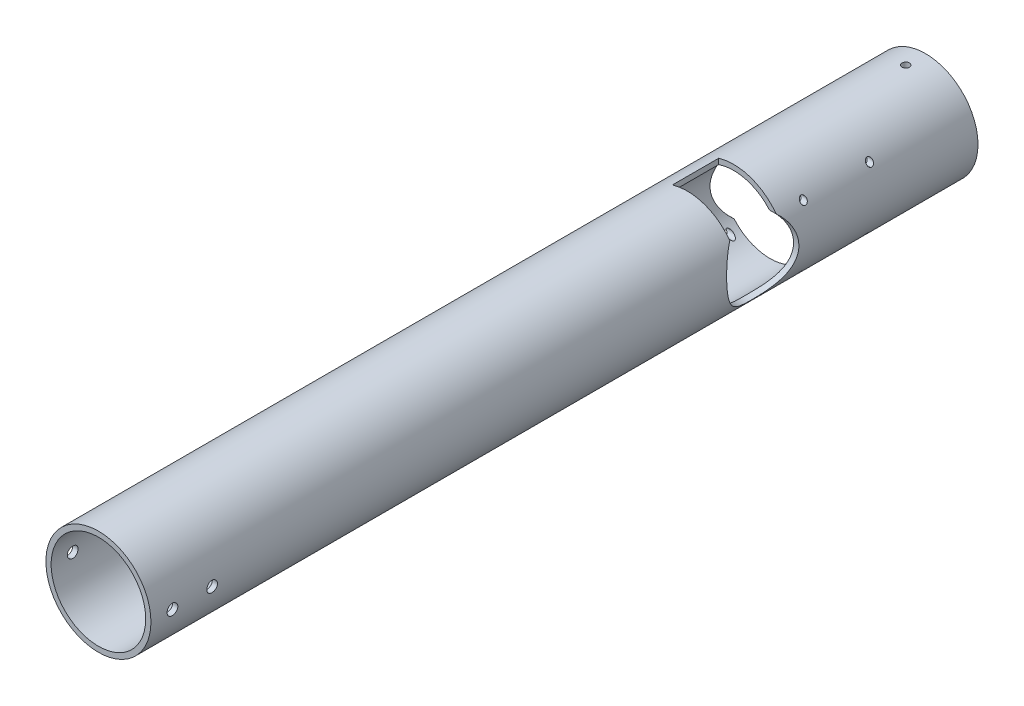
SolidWorks part; units mm, degrees
ref_plane "Front Plane" through (0, 0, 0) normal (0, 0, 1) x (1, 0, 0)
ref_plane "Top Plane" through (0, 0, 0) normal (0, 1, 0) x (1, 0, 0)
ref_plane "Right Plane" through (0, 0, 0) normal (1, 0, 0) x (0, 0, -1)
sketch "Sketch1" plane through (0, 0, 0) normal (0, 0, 1) x (1, 0, 0)
  circle A0 centre (0, 0) radius 31.75
  circle A1 centre (0, 0) radius 28.575
  dimension "D1" = 63.5
  dimension "D2" = 57.15
extrude "Boss-Extrude1" add sketch "Sketch1" along normal blind 250 and the other way blind 250 contours A1 | A0 region at (0, 0, 0)
sketch "Sketch2" plane through (0, 0, 0) normal (1, 0, 0) x (0, 0, -1)
  circle A2 centre (170, -2) radius 21.75
  dimension "D1" = 43.5
  dimension "D2" = 170
  dimension "D3" = 2
extrude "Cut-Extrude1" cut sketch "Sketch2" against normal through all
sketch "Sketch3" plane through (0, 0, 0) normal (1, 0, 0) x (0, 0, -1)
  circle A1 centre (120, 2) radius 21.75
  dimension "D1" = 120
  dimension "D2" = 43.5
  dimension "D3" = 2
extrude "Cut-Extrude2" cut sketch "Sketch3" along normal through all
sketch "Sketch5" plane through (0, 0, 0) normal (1, 0, 0) x (0, 0, -1)
  line L1 (184, -12.75) -> (156, -12.75)
  line L2 (184, -12.75) -> (184, -34.75)
  line L3 (184, -34.75) -> (156, -34.75)
  line L4 (156, -12.75) -> (156, -34.75)
  line L5 (184, -12.75) -> (156, -34.75) construction
  line L6 (184, -34.75) -> (156, -12.75) construction
  circle A0 centre (170, -2) radius 21.75 construction
  circle A1 centre (170, -2) radius 21.75 construction
  point P0 (170, -23.75)
  dimension "D1" = 28
  dimension "D2" = 22
  dimension "D3" = 170
extrude "Cut-Extrude4" cut sketch "Sketch5" against normal through all from offset 9
sketch "Sketch6" plane through (0, 0, 0) normal (1, 0, 0) x (0, 0, -1)
  line L1 (106, 34.75) -> (134, 34.75)
  line L2 (106, 34.75) -> (106, 12.75)
  line L3 (106, 12.75) -> (134, 12.75)
  line L4 (134, 34.75) -> (134, 12.75)
  line L5 (106, 34.75) -> (134, 12.75) construction
  line L6 (106, 12.75) -> (134, 34.75) construction
  circle A0 centre (120, 2) radius 21.75 construction
  circle A1 centre (120, 2) radius 21.75 construction
  point P0 (120, 23.75)
  dimension "D1" = 28
  dimension "D2" = 22
  dimension "D3" = 120
extrude "Cut-Extrude5" cut sketch "Sketch6" along normal through all from offset 9 offset against normal yes
sketch "Sketch10" plane through (0, 0, 0) normal (1, 0, 0) x (0, 0, -1)
  line L1 (210, 38) -> (130, 38)
  line L2 (210, 38) -> (210, -42)
  line L3 (210, -42) -> (130, -42)
  line L4 (130, 38) -> (130, -42)
  line L5 (210, 38) -> (130, -42) construction
  line L6 (210, -42) -> (130, 38) construction
  point P0 (170, -2)
  dimension "D1" = 80
  dimension "D2" = 80
sketch "Sketch11" plane through (0, 0, 0) normal (1, 0, 0) x (0, 0, -1)
  line L0 (210, 38) -> (130, -42) construction
  line L1 (210, -42) -> (130, 38) construction
  circle A0 centre (190, 18) radius 2
  circle A1 centre (150, 18) radius 2
  circle A2 centre (150, -22) radius 2
  circle A3 centre (190, -22) radius 2
  dimension "D5" = 4
  dimension "D6" = 4
  dimension "D7" = 4
  dimension "D8" = 4
  dimension "D1" = 20
  dimension "D2" = 20
  dimension "D3" = 20
  dimension "D4" = 20
extrude "Cut-Extrude8" cut sketch "Sketch11" against normal through all both and the other way through all
sketch "Sketch12" plane through (0, 0, 0) normal (1, 0, 0) x (0, 0, -1)
  line L1 (-250, 31.75) -> (-250, -31.75) construction
  circle A0 centre (-213, 0) radius 3.25
  circle A1 centre (-237, 0) radius 3.25
  dimension "D1" = 6.5
  dimension "D2" = 6.5
  dimension "D3" = 24
  dimension "D4" = 13
extrude "Cut-Extrude10" cut sketch "Sketch12" against normal through all both and the other way through all
sketch "Sketch13" plane through (0, 0, 0) normal (0, 1, 0) x (1, 0, 0)
  line L0 (0, -44) -> (0, 44) construction
  line L1 (28.575, 250) -> (-28.575, 250) construction
  circle A0 centre (0, 238) radius 2.25
  dimension "D2" = 4.5
  dimension "D1" = 12
extrude "Cut-Extrude11" cut sketch "Sketch13" against normal through all both and the other way through all
